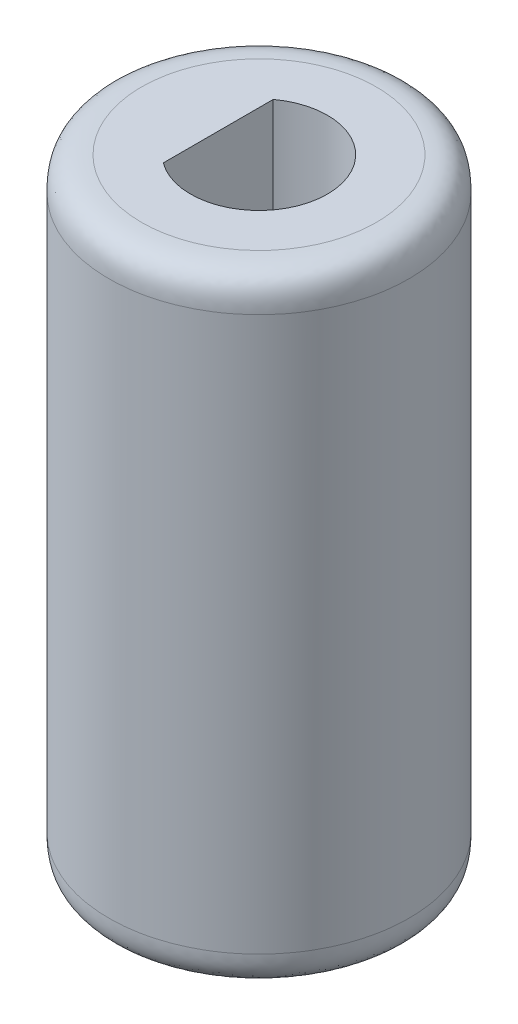
SolidWorks part; units mm, degrees
ref_plane "Front Plane" through (0, 0, 0) normal (0, 0, 1) x (1, 0, 0)
ref_plane "Top Plane" through (0, 0, 0) normal (0, 1, 0) x (1, 0, 0)
ref_plane "Right Plane" through (0, 0, 0) normal (1, 0, 0) x (0, 0, -1)
sketch "Sketch1" plane through (0, 0, 0) normal (0, 0, 1) x (1, 0, 0)
  line L0 (0, 0) -> (-9.207, 0) construction
  line L1 (-9.207, 38) -> (-9.207, 0)
  line L2 (0, 20) -> (0, 18)
  line L4 (-9.207, 38) -> (0, 38) construction
  line L5 (0, 38) -> (0, 0) construction
  line L6 (-9.207, 38) -> (-4.2, 38)
  line L7 (-9.207, 0) -> (-5.207, 0)
  line L8 (-4.2, 38) -> (-4.2, 20)
  line L9 (-4.2, 20) -> (0, 20)
  line L10 (-5.207, 0) -> (-5.207, 18)
  line L11 (-5.207, 18) -> (0, 18)
  dimension "D1" = 4.2
  dimension "D2" = 38
  dimension "D3" = 18
  dimension "D4" = 5.207
  dimension "D5" = 4
revolve "Revolve1" add sketch "Sketch1" angle 360 about L5
sketch "Sketch2" plane through (0, 18, 0) normal (0, -1, 0) x (1, 0, 0)
  line L0 (4.191, 3.09) -> (4.191, -3.09)
  circle A3 centre (0, 0) radius 5.207 construction
  circle A4 centre (0, 0) radius 5.207 construction
  circle M2 centre (0, 0) radius 5.207
  dimension "D1" = 1.016
sketch "Sketch3" plane through (0, 20, 0) normal (0, 1, 0) x (1, 0, 0)
  line L0 (-2.5, 3.3749) -> (-2.5, -3.3749)
  circle A0 centre (0, 0) radius 4.2 construction
  circle A2 centre (0, 0) radius 4.2
  arc A3 (-2.5, 3.3749) -> (-2.5, -3.3749) centre (0, 0) ccw
  dimension "D1" = 2.5
  dimension "D2" = 0
extrude "Boss-Extrude1" add sketch "Sketch3" along normal up to surface (18 mm away) up to face at (-9.207, 38, 0)
extrude "Boss-Extrude2" add sketch "Sketch2" along normal up to surface (18 mm away) contours L0 M2 region at (4.601, 18, 0) up to face at (-5.207, 0, 0)
fillet "Fillet1" radius 2 2 edges at (-9.207, 38, 0) (-9.207, 0, 0) curvature continuous yes
